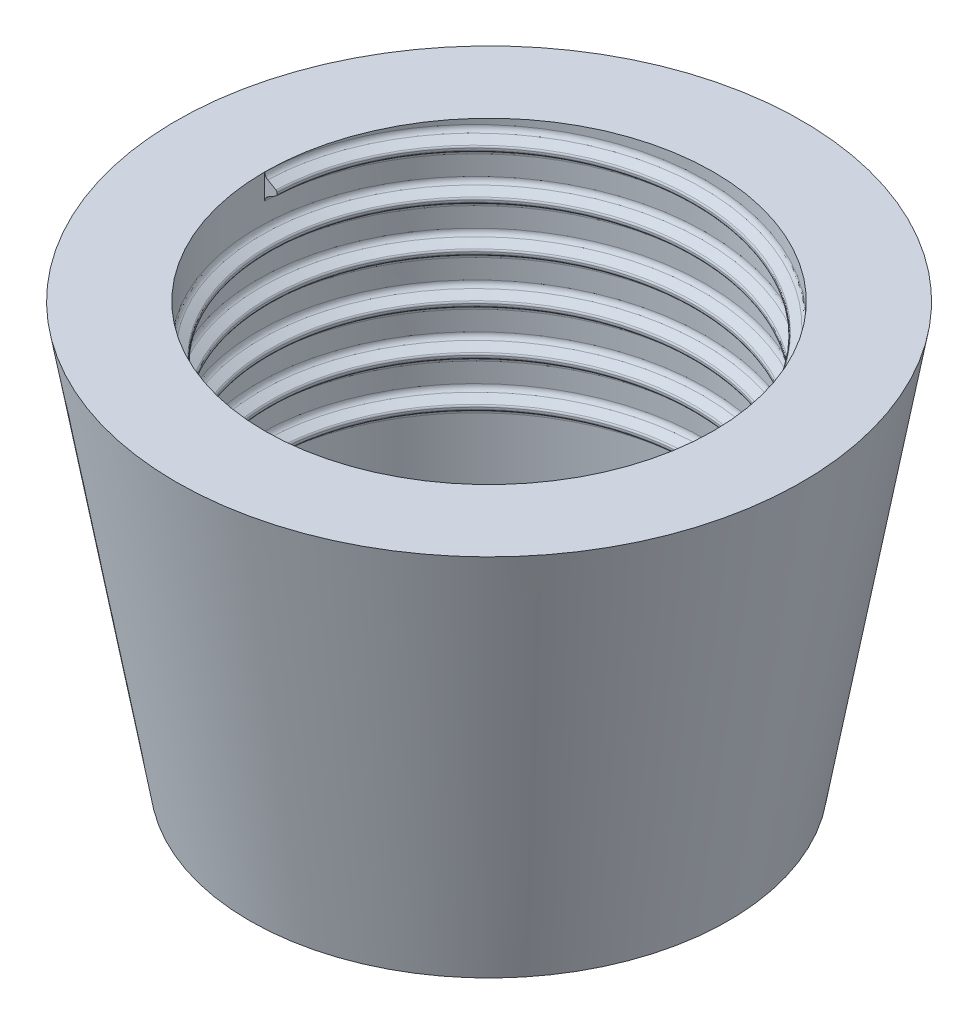
SolidWorks part; units mm, degrees
ref_plane "Front Plane" through (0, 0, 0) normal (0, 0, 1) x (1, 0, 0)
ref_plane "Top Plane" through (0, 0, 0) normal (0, 1, 0) x (1, 0, 0)
ref_plane "Right Plane" through (0, 0, 0) normal (1, 0, 0) x (0, 0, -1)
sketch "Sketch1" plane through (0, 0, 0) normal (0, 1, 0) x (1, 0, 0)
  circle A0 centre (0, 0) radius 16
extrude "Boss-Extrude1" add sketch "Sketch1" along normal blind 20 draft 10 contours A0 draft outward yes
sketch "Sketch2" plane through (0, 20, 0) normal (0, 1, 0) x (1, 0, 0)
  circle A0 centre (0, 0) radius 14
sketch "Sketch10" plane through (0, 20, 0) normal (0, 1, 0) x (1, 0, 0)
  circle A0 centre (0, 0) radius 14
extrude "Cut-Extrude2" cut sketch "Sketch10" against normal blind 20
thread "Thread1" pitch 2.1167 method extrude profile "Thread Profile2" start angle 0, offset 0, length 16, pitch 2.8, diameter 28
ref_plane "Plane2" through (-14, 20, 0) normal (0, 0, -1) x (1, 0, 0)
sketch "Thread Profile2" plane through (-14, 20, 0) normal (0, 0, -1) x (1, 0, 0)
  line L0 (0, 0) -> (0, 2.1167) construction
  line L1 (0, 0) -> (0, 1.5829)
  line L2 (0.381, 1.5829) -> (0.762, 1.5829) construction
  line L3 (0.762, 0.8497) -> (0.762, 0.7332)
  line L4 (0.6985, 0.9597) -> (0.1905, 1.253)
  line L5 (0.6985, 0.6232) -> (0.1905, 0.33)
  line L6 (0.381, 0) -> (0.762, 0) construction
  arc A0 (0.1905, 1.253) -> (0, 1.5829) centre (0.381, 1.5829) cw
  arc A1 (0.1905, 0.33) -> (0, 0) centre (0.381, 0) ccw
  arc A2 (0.762, 0.7332) -> (0.6985, 0.6232) centre (0.635, 0.7332) cw
  arc A3 (0.762, 0.8497) -> (0.6985, 0.9597) centre (0.635, 0.8497) ccw
  point P10 (0.762, 0.923)
  point P17 (0.762, 0.6599)
  point P18 (0, 1.363)
  point P19 (0, 0.22)
  point P20 (0, 0)
  dimension "RootFillet1" = 0.381
  dimension "RootFillet2" = 0.381
  dimension "CrestFillet2" = 0.127
  dimension "CrestFillet1" = 0.127
  dimension "Pitch" = 2.1167
  dimension "Angle1" = 30
  dimension "Angle2" = 30
  dimension "a" = 1.143
  dimension "b" = 0.762
  dimension "c" = 0.2631
sketch "Sketch19" plane through (0, 0, 0) normal (0, -1, 0) x (-1, 0, 0)
  circle A0 centre (0, 0) radius 13
  circle A1 centre (0, 0) radius 6.75
sketch "Sketch20" plane through (0, 0, 0) normal (0, -1, 0) x (1, 0, 0)
  circle A0 centre (0, 0) radius 16
extrude "Boss-Extrude3" add sketch "Sketch20" along normal blind 6 draft 10
extrude "Cut-Extrude3" cut sketch "Sketch19" along normal blind 3 contours A1
sketch "Sketch127" plane through (0, -3, 0) normal (0, 1, 0) x (1, 0, 0)
  circle A0 centre (0, 0) radius 5
extrude "Cut-Extrude4" cut sketch "Sketch127" against normal blind 3
